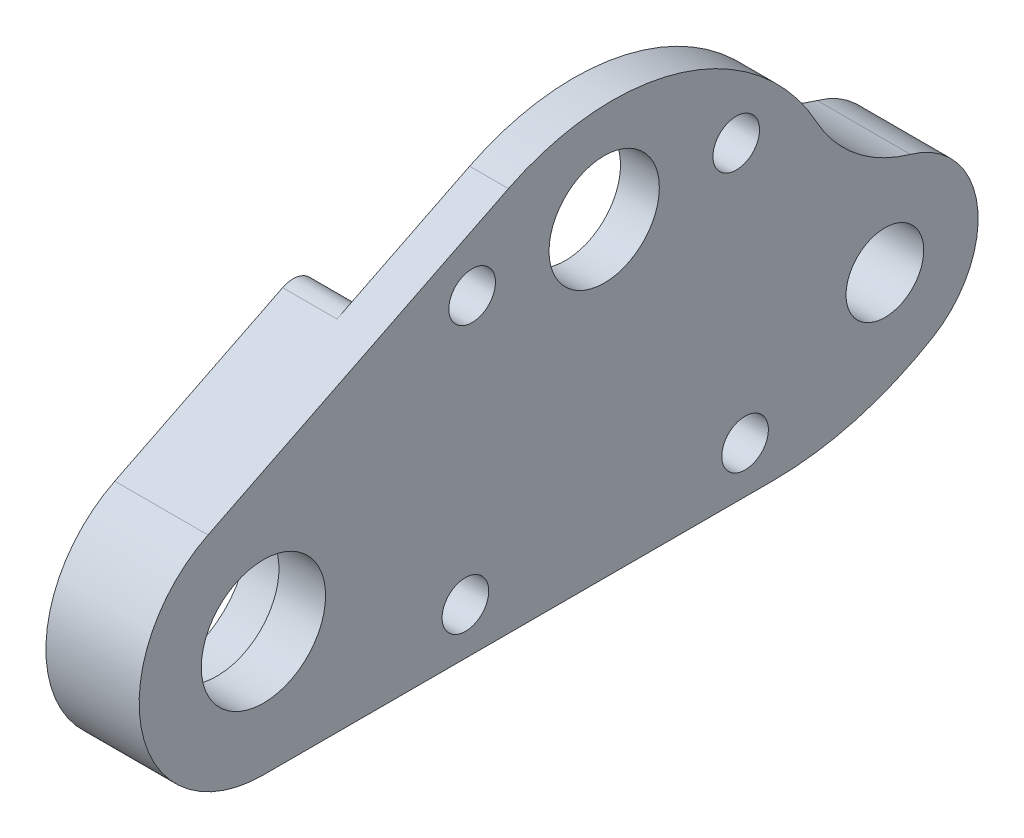
SolidWorks part; units mm, degrees
material "1060 Alloy"
ref_plane "Front Plane" through (0, 0, 0) normal (0, 0, 1) x (1, 0, 0)
ref_plane "Top Plane" through (0, 0, 0) normal (0, 1, 0) x (1, 0, 0)
ref_plane "Right Plane" through (0, 0, 0) normal (1, 0, 0) x (0, 0, -1)
sketch "Sketch27" plane through (0, 0, 0) normal (1, 0, 0) x (0, 0, -1)
  line L0 (6.4321, 49.1603) -> (25.768, 58.7953)
  line L3 (40.4317, 54) -> (23.4317, 54) construction
  line L6 (42.7889, 34) -> (10, 34)
  line L8 (0, 0) -> (60, 0) construction
  line L9 (0, 0) -> (0, 58) construction
  line L10 (0, 58) -> (60, 58) construction
  line L11 (60, 0) -> (60, 58) construction
  arc A0 (6.4321, 49.1603) -> (10, 34) centre (10, 42) ccw
  circle A1 centre (31.9317, 54) radius 12.5 construction
  arc A2 (45.6106, 52.5814) -> (25.768, 58.7953) centre (32.4579, 45.3698) ccw
  circle A3 centre (31.9317, 54) radius 3.55
  arc A4 (51.6421, 47.7709) -> (53.0905, 36.8571) centre (50, 42) cw
  circle A5 centre (10, 42) radius 4
  circle A6 centre (50, 42) radius 2.5
  circle A7 centre (40.4317, 54) radius 1.5
  circle A8 centre (23.4317, 54) radius 1.5
  circle A9 centre (40.4317, 54) radius 3.25 construction
  circle A10 centre (23.4317, 54) radius 3.25 construction
  arc A11 (53.0905, 36.8571) -> (42.7889, 34) centre (42.7889, 54) cw
  arc A12 (51.6421, 47.7709) -> (45.6106, 52.5814) centre (54.379, 57.3891) cw
  dimension "D9" = 6
  dimension "D10" = 5
  dimension "D11" = 15
  dimension "D12" = 8
  dimension "D13" = 8
  dimension "D14" = 20
  dimension "D15" = 25
  dimension "D6" = 25
  dimension "D17" = 7.1
  dimension "D16" = 3
  dimension "D19" = 6.5
  dimension "D20" = 10
  dimension "D1" = 60
  dimension "D2" = 58
  dimension "D3" = 42
  dimension "D4" = 10
  dimension "D5" = 42
  dimension "D7" = 50
  dimension "D8" = 12
  dimension "D18" = 8.5
extrude "Boss-Extrude1" add sketch "Sketch27" along normal blind 6
sketch "Sketch47" plane through (0, 0, 0) normal (-1, 0, 0) x (0, 0, 1)
  circle A0 centre (-10, 42) radius 4.99
  dimension "D1" = 9.98
extrude "Cut-Extrude8" cut sketch "Sketch47" against normal blind 3
sketch "Sketch48" plane through (0, 0, 0) normal (-1, 0, 0) x (0, 0, 1)
  line L1 (-25.768, 58.7953) -> (-6.4321, 49.1603) construction
  line L2 (-46.7042, 50.9784) -> (-37.7377, 64.7597)
  line L4 (-37.7377, 64.7597) -> (-17.2355, 54.5436)
  arc A0 (-44.004, 50.5703) -> (-19.402, 53.2863) centre (-31.9317, 54) ccw
  arc A1 (-44.004, 50.5703) -> (-46.7042, 50.9784) centre (-45.4469, 50.1604) ccw
  arc A2 (-19.402, 53.2863) -> (-17.2355, 54.5436) centre (-17.9044, 53.201) cw
  arc A3 (-51.6421, 47.7709) -> (-45.6106, 52.5814) centre (-54.379, 57.3891) ccw construction
  arc A4 (-25.768, 58.7953) -> (-45.6106, 52.5814) centre (-32.4579, 45.3698) ccw construction
  dimension "D1" = 12.55
  dimension "D2" = 1.5
  dimension "D3" = 1.5
extrude "Cut-Extrude10" cut sketch "Sketch48" against normal blind 3.5
sketch "Sketch49" plane through (0, 0, 0) normal (-1, 0, 0) x (0, 0, 1)
  line L0 (-44, 34) -> (-20, 34)
  line L1 (-44, 34) -> (-44, 40)
  line L2 (-20, 34) -> (-20, 40)
  line L3 (-44, 40) -> (-20, 40)
  line L4 (-10, 34) -> (-42.7889, 34) construction
  circle A0 centre (-50, 42) radius 2.5 construction
  dimension "D1" = 6
  dimension "D2" = 24
  dimension "D3" = 6
extrude "Cut-Extrude11" cut sketch "Sketch49" against normal blind 3
sketch "Sketch50" plane through (0, 0, 0) normal (-1, 0, 0) x (0, 0, 1)
  circle A0 centre (-44, 40) radius 1.5
  circle A1 centre (-20, 40) radius 1.5
  dimension "D1" = 3
extrude "Cut-Extrude12" cut sketch "Sketch50" against normal up to surface (3 mm away) up to face at (3, 36.4055, -34.1578)
fillet "Fillet1" radius 3 4 edges at (1.5, 38.5, -44) (1.5, 38.5, -20) (1.5, 40, -21.5) (1.5, 40, -42.5)
sketch "Sketch51" plane through (3, 0, 0) normal (-1, 0, 0) x (0, 0, 1)
  line L0 (-42.7889, 34) -> (-20, 34) construction
  line L1 (-44, 36.6459) -> (-44, 34.0367) construction
  line L2 (-20, 34) -> (-20, 36.6459) construction
  circle A0 centre (-41, 37) radius 1.5
  circle A1 centre (-23, 37) radius 1.5
  dimension "D1" = 3
  dimension "D2" = 3
  dimension "D3" = 3
  dimension "D4" = 3
  dimension "D5" = 3
extrude "Cut-Extrude13" cut sketch "Sketch51" against normal up to next
